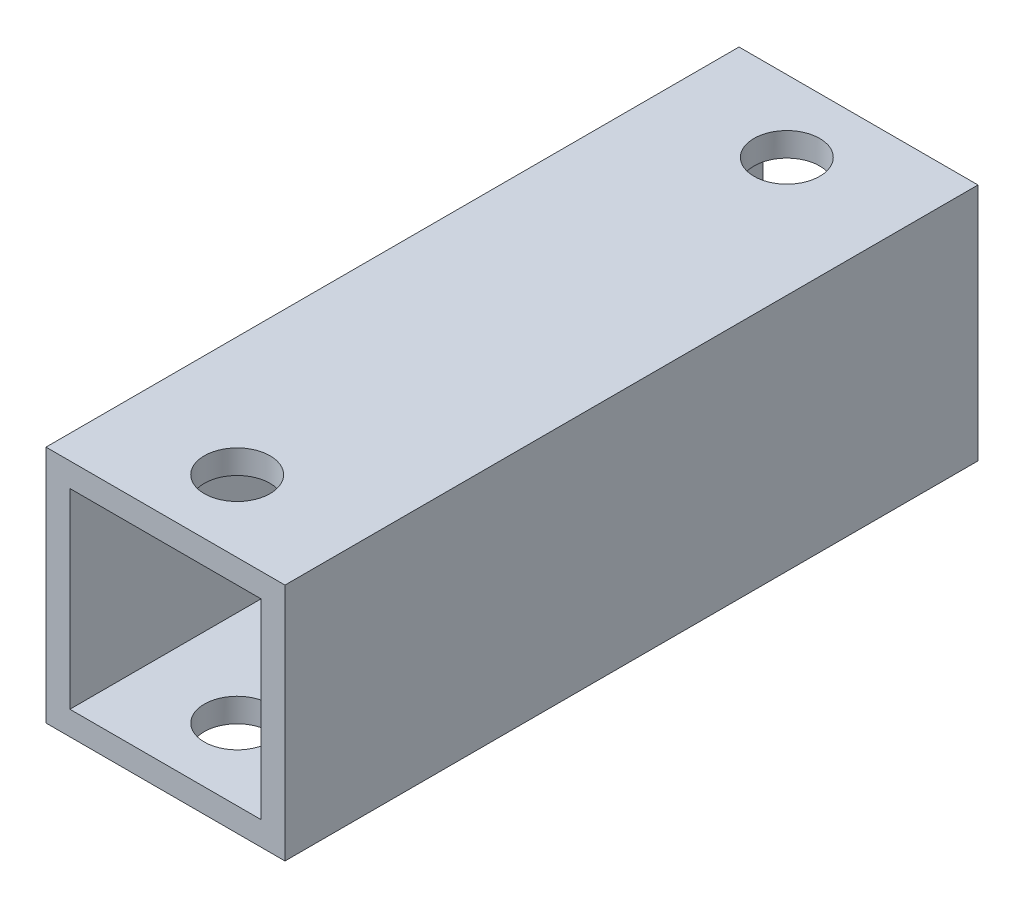
SolidWorks part; units mm, degrees
ref_plane "前视基准面" through (0, 0, 0) normal (0, 0, 1) x (1, 0, 0)
ref_plane "上视基准面" through (0, 0, 0) normal (0, 1, 0) x (1, 0, 0)
ref_plane "右视基准面" through (0, 0, 0) normal (1, 0, 0) x (0, 0, -1)
other "Configuration Table"
sketch "草图1" plane through (0, 0, 0) normal (0, 0, 1) x (1, 0, 0)
  line L1 (-10, -10) -> (10, -10)
  line L2 (-10, -10) -> (-10, 10)
  line L3 (-10, 10) -> (10, 10)
  line L4 (10, -10) -> (10, 10)
  line L5 (-10, -10) -> (10, 10) construction
  line L6 (-10, 10) -> (10, -10) construction
  line L7 (-8, -8) -> (8, -8)
  line L8 (-8, -8) -> (-8, 8)
  line L9 (-8, 8) -> (8, 8)
  line L10 (8, -8) -> (8, 8)
  line L11 (-8, -8) -> (8, 8) construction
  line L12 (-8, 8) -> (8, -8) construction
  point P0 (0, 0)
  point P6 (0, 0)
  dimension "D1" = 20
  dimension "D2" = 20
  dimension "D3" = 2
  dimension "D4" = 2
extrude "凸台-拉伸1" add sketch "草图1" along normal blind 58
sketch "草图2" plane through (0, 10, 0) normal (0, 1, 0) x (1, 0, 0)
  line L0 (0, 0) -> (0, -58) construction
  line L1 (10, 0) -> (-10, 0) construction
  line L2 (10, -58) -> (-10, -58) construction
  line L3 (10, -29) -> (-10, -29) construction
  line L4 (10, -58) -> (10, 0) construction
  line L5 (-10, -58) -> (-10, 0) construction
  circle A0 centre (0, -6) radius 2.75
  circle A1 centre (0, -52) radius 2.75
  dimension "D1" = 5.5
  dimension "D2" = 23
extrude "切除-拉伸1" cut sketch "草图2" against normal through all
